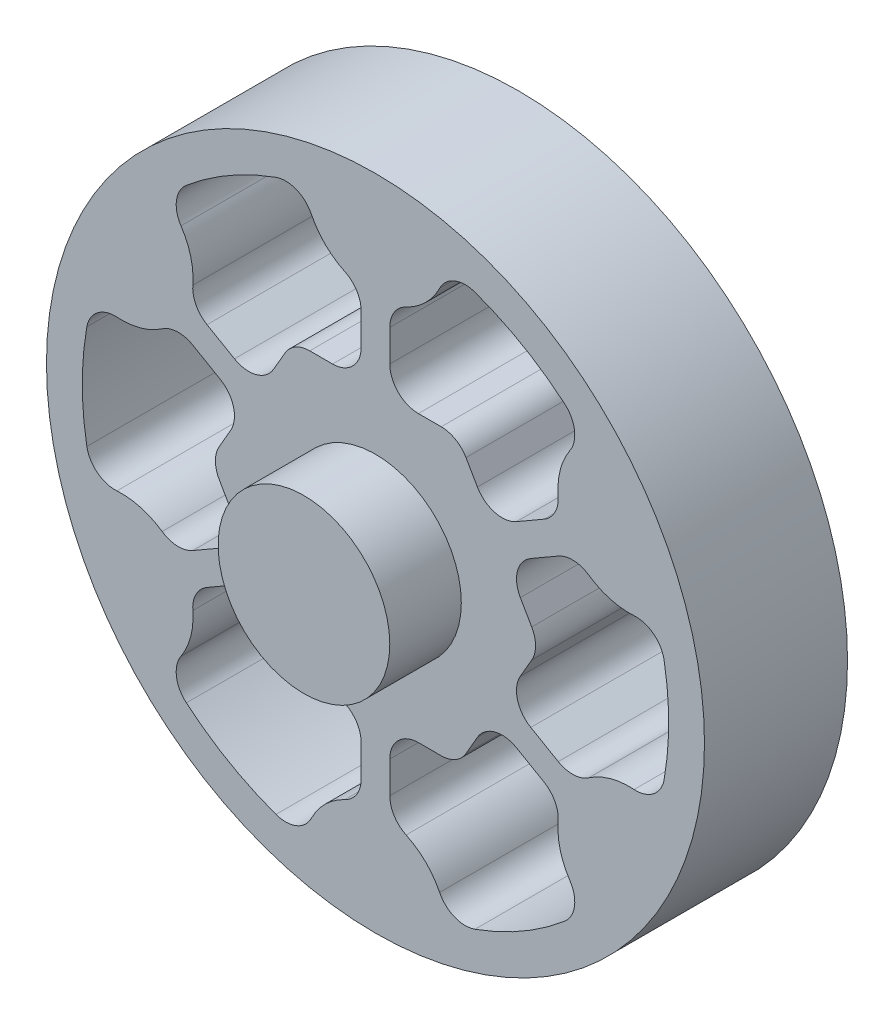
SolidWorks part; units mm, degrees
ref_plane "Front Plane" through (0, 0, 0) normal (0, 0, 1) x (1, 0, 0)
ref_plane "Top Plane" through (0, 0, 0) normal (0, 1, 0) x (1, 0, 0)
ref_plane "Right Plane" through (0, 0, 0) normal (1, 0, 0) x (0, 0, -1)
sketch "Sketch1" plane through (0, 0, 0) normal (0, 0, 1) x (1, 0, 0)
  line L0 (0, 0) -> (0, 22127.0424) construction
  line L1 (0, 0) -> (22127.0424, 0) construction
  line L2 (-1, 14.1754) -> (-1, 11.9593)
  line L3 (4.5953, 9.9593) -> (3, 9.9593)
  line L4 (-6.3274, 8.9593) -> (-7.125, 7.5777)
  line L5 (-10.9226, -1) -> (-10.125, -2.3816)
  line L6 (-4.5953, -9.9593) -> (-3, -9.9593)
  line L7 (6.3274, -8.9593) -> (7.125, -7.5777)
  line L8 (10.9226, 1) -> (10.125, 2.3816)
  line L9 (1, 14.1754) -> (1, 11.9593)
  line L10 (11.7763, 7.9537) -> (9.8571, 6.8457)
  line L11 (12.7763, 6.2217) -> (10.8571, 5.1136)
  line L12 (12.7763, -6.2217) -> (10.8571, -5.1136)
  line L13 (11.7763, -7.9537) -> (9.8571, -6.8457)
  line L14 (1, -14.1754) -> (1, -11.9593)
  line L15 (-1, -14.1754) -> (-1, -11.9593)
  line L16 (-11.7763, -7.9537) -> (-9.8571, -6.8457)
  line L17 (-12.7763, -6.2217) -> (-10.8571, -5.1136)
  line L18 (-12.7763, 6.2217) -> (-10.8571, 5.1136)
  line L19 (-11.7763, 7.9537) -> (-9.8571, 6.8457)
  line L20 (-10.125, 2.3816) -> (-10.9226, 1)
  line L21 (7.125, 7.5777) -> (6.3274, 8.9593)
  line L22 (-3, 9.9593) -> (-4.5953, 9.9593)
  line L23 (-7.125, -7.5777) -> (-6.3274, -8.9593)
  line L24 (10.125, -2.3816) -> (10.9226, -1)
  line L25 (3, -9.9593) -> (4.5953, -9.9593)
  circle A0 centre (0, 0) radius 11.5 construction
  arc A1 (-6.956, 19.2838) -> (-13.2223, 15.6659) centre (0, 0) ccw
  circle A2 centre (0, 0) radius 23
  arc A3 (-4.4838, 18.2875) -> (-2.1429, 15.9825) centre (0, 20.5) ccw
  arc A4 (13.5955, 13.0268) -> (12.7698, 9.847) centre (17.7535, 10.25) ccw
  arc A5 (18.0793, -5.2606) -> (14.9126, -6.1355) centre (17.7535, -10.25) ccw
  arc A6 (4.4838, -18.2875) -> (2.1429, -15.9825) centre (0, -20.5) ccw
  arc A7 (-13.5955, -13.0268) -> (-12.7698, -9.847) centre (-17.7535, -10.25) ccw
  arc A8 (-18.0793, 5.2606) -> (-14.9126, 6.1355) centre (-17.7535, 10.25) ccw
  arc A9 (13.2223, 15.6659) -> (6.956, 19.2838) centre (0, 0) ccw
  arc A10 (20.1782, -3.6178) -> (20.1782, 3.6178) centre (0, 0) ccw
  arc A11 (6.956, -19.2838) -> (13.2223, -15.6659) centre (0, 0) ccw
  arc A12 (-13.2223, -15.6659) -> (-6.956, -19.2838) centre (0, 0) ccw
  arc A13 (-20.1782, 3.6178) -> (-20.1782, -3.6178) centre (0, 0) ccw
  arc A14 (-12.7698, 9.847) -> (-13.5955, 13.0268) centre (-17.7535, 10.25) ccw
  arc A15 (2.1429, 15.9825) -> (4.4838, 18.2875) centre (0, 20.5) ccw
  arc A16 (14.9126, 6.1355) -> (18.0793, 5.2606) centre (17.7535, 10.25) ccw
  arc A17 (12.7698, -9.847) -> (13.5955, -13.0268) centre (17.7535, -10.25) ccw
  arc A18 (-14.9126, -6.1355) -> (-18.0793, -5.2606) centre (-17.7535, -10.25) ccw
  arc A19 (-2.1429, -15.9825) -> (-4.4838, -18.2875) centre (0, -20.5) ccw
  arc A20 (-9.8571, 6.8457) -> (-7.125, 7.5777) centre (-8.8571, 8.5777) ccw
  arc A21 (-10.8571, 5.1136) -> (-10.125, 2.3816) centre (-11.8571, 3.3816) cw
  arc A22 (-10.8571, -5.1136) -> (-10.125, -2.3816) centre (-11.8571, -3.3816) ccw
  arc A23 (-9.8571, -6.8457) -> (-7.125, -7.5777) centre (-8.8571, -8.5777) cw
  arc A24 (-1, -11.9593) -> (-3, -9.9593) centre (-3, -11.9593) ccw
  arc A25 (1, -11.9593) -> (3, -9.9593) centre (3, -11.9593) cw
  arc A26 (9.8571, -6.8457) -> (7.125, -7.5777) centre (8.8571, -8.5777) ccw
  arc A27 (10.8571, -5.1136) -> (10.125, -2.3816) centre (11.8571, -3.3816) cw
  arc A28 (10.8571, 5.1136) -> (10.125, 2.3816) centre (11.8571, 3.3816) ccw
  arc A29 (9.8571, 6.8457) -> (7.125, 7.5777) centre (8.8571, 8.5777) cw
  arc A30 (1, 11.9593) -> (3, 9.9593) centre (3, 11.9593) ccw
  arc A31 (-1, 11.9593) -> (-3, 9.9593) centre (-3, 11.9593) cw
  arc A32 (10.9226, -1) -> (10.9226, 1) centre (9.1906, 0) ccw
  arc A33 (4.5953, -9.9593) -> (6.3274, -8.9593) centre (4.5953, -7.9593) ccw
  arc A34 (-6.3274, -8.9593) -> (-4.5953, -9.9593) centre (-4.5953, -7.9593) ccw
  arc A35 (-10.9226, 1) -> (-10.9226, -1) centre (-9.1906, 0) ccw
  arc A36 (-4.5953, 9.9593) -> (-6.3274, 8.9593) centre (-4.5953, 7.9593) ccw
  arc A37 (4.5953, 9.9593) -> (6.3274, 8.9593) centre (4.5953, 7.9593) cw
  arc A38 (-20.1782, 3.6178) -> (-18.0793, 5.2606) centre (-18.2096, 3.2649) cw
  arc A39 (-13.2223, 15.6659) -> (-13.5955, 13.0268) centre (-11.9323, 14.1376) ccw
  arc A40 (-13.2223, -15.6659) -> (-13.5955, -13.0268) centre (-11.9323, -14.1376) cw
  arc A41 (-18.0793, -5.2606) -> (-20.1782, -3.6178) centre (-18.2096, -3.2649) cw
  arc A42 (-4.4838, -18.2875) -> (-6.956, -19.2838) centre (-6.2773, -17.4024) cw
  arc A43 (6.956, -19.2838) -> (4.4838, -18.2875) centre (6.2773, -17.4024) cw
  arc A44 (20.1782, -3.6178) -> (18.0793, -5.2606) centre (18.2096, -3.2649) cw
  arc A45 (13.5955, -13.0268) -> (13.2223, -15.6659) centre (11.9323, -14.1376) cw
  arc A46 (4.4838, 18.2875) -> (6.956, 19.2838) centre (6.2773, 17.4024) cw
  arc A47 (-11.7763, 7.9537) -> (-12.7698, 9.847) centre (-10.7763, 9.6858) cw
  arc A48 (-12.7763, 6.2217) -> (-14.9126, 6.1355) centre (-13.7763, 4.4896) ccw
  arc A49 (-12.7763, -6.2217) -> (-14.9126, -6.1355) centre (-13.7763, -4.4896) cw
  arc A50 (-11.7763, -7.9537) -> (-12.7698, -9.847) centre (-10.7763, -9.6858) ccw
  arc A51 (-1, -14.1754) -> (-2.1429, -15.9825) centre (-3, -14.1754) cw
  arc A52 (1, -14.1754) -> (2.1429, -15.9825) centre (3, -14.1754) ccw
  arc A53 (11.7763, -7.9537) -> (12.7698, -9.847) centre (10.7763, -9.6858) cw
  arc A54 (12.7763, -6.2217) -> (14.9126, -6.1355) centre (13.7763, -4.4896) ccw
  arc A55 (12.7763, 6.2217) -> (14.9126, 6.1355) centre (13.7763, 4.4896) cw
  arc A56 (11.7763, 7.9537) -> (12.7698, 9.847) centre (10.7763, 9.6858) ccw
  arc A57 (-4.4838, 18.2875) -> (-6.956, 19.2838) centre (-6.2773, 17.4024) ccw
  arc A58 (1, 14.1754) -> (2.1429, 15.9825) centre (3, 14.1754) cw
  arc A59 (-1, 14.1754) -> (-2.1429, 15.9825) centre (-3, 14.1754) ccw
  arc A60 (13.2223, 15.6659) -> (13.5955, 13.0268) centre (11.9323, 14.1376) cw
  arc A61 (18.0793, 5.2606) -> (20.1782, 3.6178) centre (18.2096, 3.2649) cw
  circle A62 centre (0, 0) radius 6
  point P54 (0, 0)
  point P81 (-1, 9.9593)
  point P84 (11.5, 0)
  point P91 (-11.5, 0)
  point P138 (1, 15.601)
  dimension "D2" = 41
  dimension "D3" = 46
  dimension "D4" = 10
  dimension "D6" = 2
  dimension "D7" = 12
  dimension "D1" = 23
  dimension "D5" = 2
extrude "Boss-Extrude1" add sketch "Sketch1" along normal mid plane 20 contours A62
extrude "Boss-Extrude3" add sketch "Sketch1<7>" along normal mid plane 10
sketch "Sketch1<7>" plane through (0, 0, 0) normal (0, 0, 1) x (1, 0, 0) same geometry as "Sketch1"
